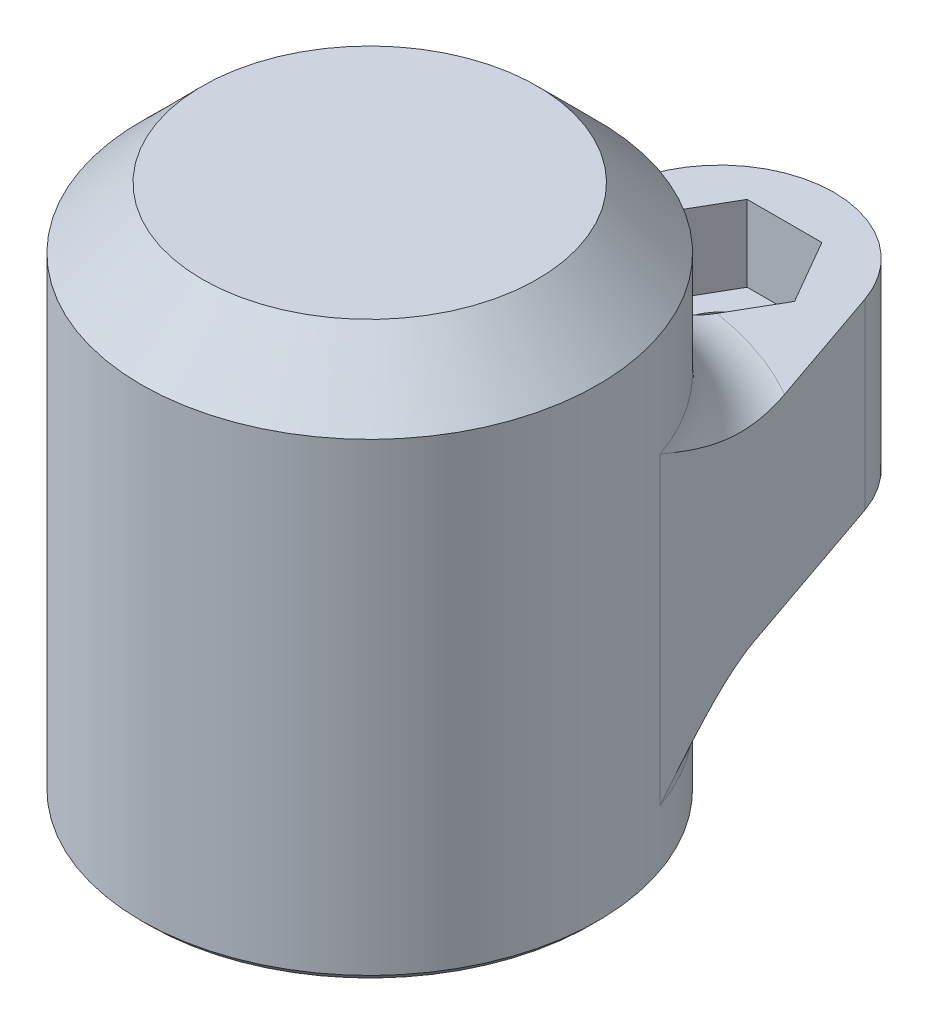
SolidWorks part; units mm, degrees
ref_plane "Front Plane" through (0, 0, 0) normal (0, 0, 1) x (1, 0, 0)
ref_plane "Top Plane" through (0, 0, 0) normal (0, 1, 0) x (1, 0, 0)
ref_plane "Right Plane" through (0, 0, 0) normal (1, 0, 0) x (0, 0, -1)
sketch "Sketch5" plane through (0, 0, 0) normal (0, 1, 0) x (1, 0, 0)
  circle A0 centre (0, 0) radius 15
  dimension "D1" = 30
extrude "Boss-Extrude3" add sketch "Sketch5" along normal blind 35
sketch "Sketch7" plane through (0, 0, 0) normal (1, 0, 0) x (0, 0, -1)
  line L0 (0, 0) -> (12, 0)
  line L1 (-15, 0) -> (15, 0) construction
  line L2 (12, 0) -> (12, 5)
  line L3 (12, 5) -> (7.5, 9.5)
  line L4 (7.5, 9.5) -> (7.5, 30)
  line L5 (7.5, 30) -> (0, 30)
  line L6 (0, 30) -> (0, 0)
  dimension "D1" = 5
  dimension "D2" = 12
  dimension "D3" = 45
  dimension "D4" = 30
  dimension "D5" = 7.5
revolve "Cut-Revolve1" cut sketch "Sketch7" angle 360 about L6
sketch "Sketch8" plane through (0, 35, 0) normal (0, 1, 0) x (1, 0, 0)
  line L0 (0, 0) -> (0, 23) construction
  circle A0 centre (0, 23) radius 7.5
  circle A1 centre (0, 23) radius 2.75
  dimension "D1" = 5.5
  dimension "D2" = 15
  dimension "D3" = 23
extrude "Boss-Extrude4" add sketch "Sketch8" against normal blind 15 from offset 15.8 separate body offset against normal yes
chamfer "Chamfer1" distance 3 angle 45 1 edges at (0, 4.2, -15.5)
sketch "Sketch9" plane through (0, 19.2, 0) normal (0, 1, 0) x (1, 0, 0)
  line L0 (7.09, 25.4457) -> (14.1801, 4.8913)
  line L1 (-7.09, 25.4457) -> (-14.1801, 4.8913)
  circle A0 centre (0, 0) radius 15 construction
  circle A1 centre (0, 23) radius 7.5 construction
  arc A2 (14.1801, 4.8913) -> (-14.1801, 4.8913) centre (0, 0) ccw
  arc A3 (-7.09, 25.4457) -> (7.09, 25.4457) centre (0, 23) ccw
extrude "Boss-Extrude5" add sketch "Sketch9" against normal blind 12
fillet "Fillet1" radius 5 1 edges at (0, 19.2, -15)
sketch "Sketch10" plane through (0, 19.2, 0) normal (0, 1, 0) x (1, 0, 0)
  line L0 (-16.5, 0) -> (16.5, 0) construction
  line L1 (4.9075, 23) -> (2.4537, 27.25)
  line L2 (2.4537, 27.25) -> (-2.4537, 27.25)
  line L3 (-2.4537, 27.25) -> (-4.9075, 23)
  line L4 (-4.9075, 23) -> (-2.4537, 18.75)
  line L5 (-2.4537, 18.75) -> (2.4537, 18.75)
  line L6 (2.4537, 18.75) -> (4.9075, 23)
  circle A0 centre (0, 23) radius 4.25 construction
  dimension "D1" = 8.5
extrude "Cut-Extrude1" cut sketch "Sketch10" against normal blind 5 and the other way blind 12
sketch "Sketch11" plane through (0, 0, 0) normal (0, 0, 1) x (1, 0, 0)
  line L0 (-7.5, 23.5) -> (-5.5, 23.5)
  line L1 (-7.5, 30) -> (-7.5, 9.5) construction
  line L3 (-5.5, 23.5) -> (-5.5, 28.4)
  line L4 (-5.5, 28.4) -> (0, 28.4)
  line L5 (0, 28.4) -> (0, 35)
  line L6 (15, 35) -> (-15, 35) construction
  line L7 (0, 35) -> (-7.5, 35)
  line L8 (-7.5, 35) -> (-7.5, 23.5)
  line L10 (-7.5, 30) -> (7.5, 30) construction
  dimension "D1" = 1.6
  dimension "D2" = 11.5
  dimension "D3" = 2
revolve "Revolve1" add sketch "Sketch11" angle 360 about L5
chamfer "Chamfer2" distance 4 angle 45 1 edges at (0, 35, 15)
chamfer "Chamfer3" distance 0.5 angle 45 1 edges at (0, 0, 15)
fillet "Fillet2" radius 3 1 edges at (0, 7.2, -15)
fillet "Fillet3" radius 0.9 1 edges at (0, 23.5, -5.5)
